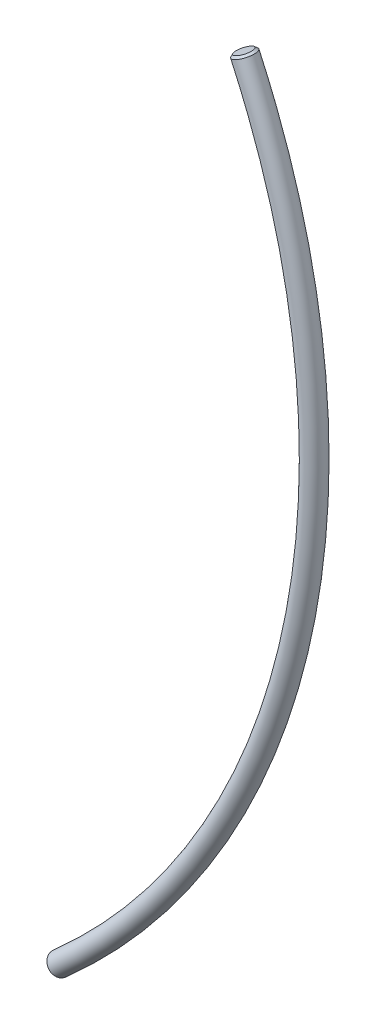
SolidWorks part; units mm, degrees
material "Aço cromo inoxidável"
ref_plane "Plano frontal" through (0, 0, 0) normal (0, 0, 1) x (1, 0, 0)
ref_plane "Plano superior" through (0, 0, 0) normal (0, 1, 0) x (1, 0, 0)
ref_plane "Plano direito" through (0, 0, 0) normal (1, 0, 0) x (0, 0, -1)
sketch "Esboço1" plane through (0, 0, 0) normal (0, 0, 1) x (1, 0, 0)
  line L0 (98.3913, 58.6907) -> (200.7619, 82.0412) construction
  line L1 (165.0792, 66.2094) -> (172.0404, 67.7972) construction
  line L2 (163.4113, 73.5216) -> (166.747, 58.8972) construction
  line L3 (173.7083, 60.485) -> (170.3725, 75.1094) construction
  arc A0 (114.6659, -117.0063) -> (158.8448, 92.9937) centre (-3.5, 17.5) ccw
  circle A1 centre (-3.5, 17.5) radius 1.5 construction
  point P11 (168.5598, 67.0033)
  dimension "D1" = 210
  dimension "D2" = 20
sweep "Varredura1" add path "Esboço1" circular profile diameter 5 parameters "D3"=5
chamfer "Chanfro1" distance 0.5 angle 45 2 edges at (156.5779, 91.9395, 0) (113.0159, -115.1281, 0)
